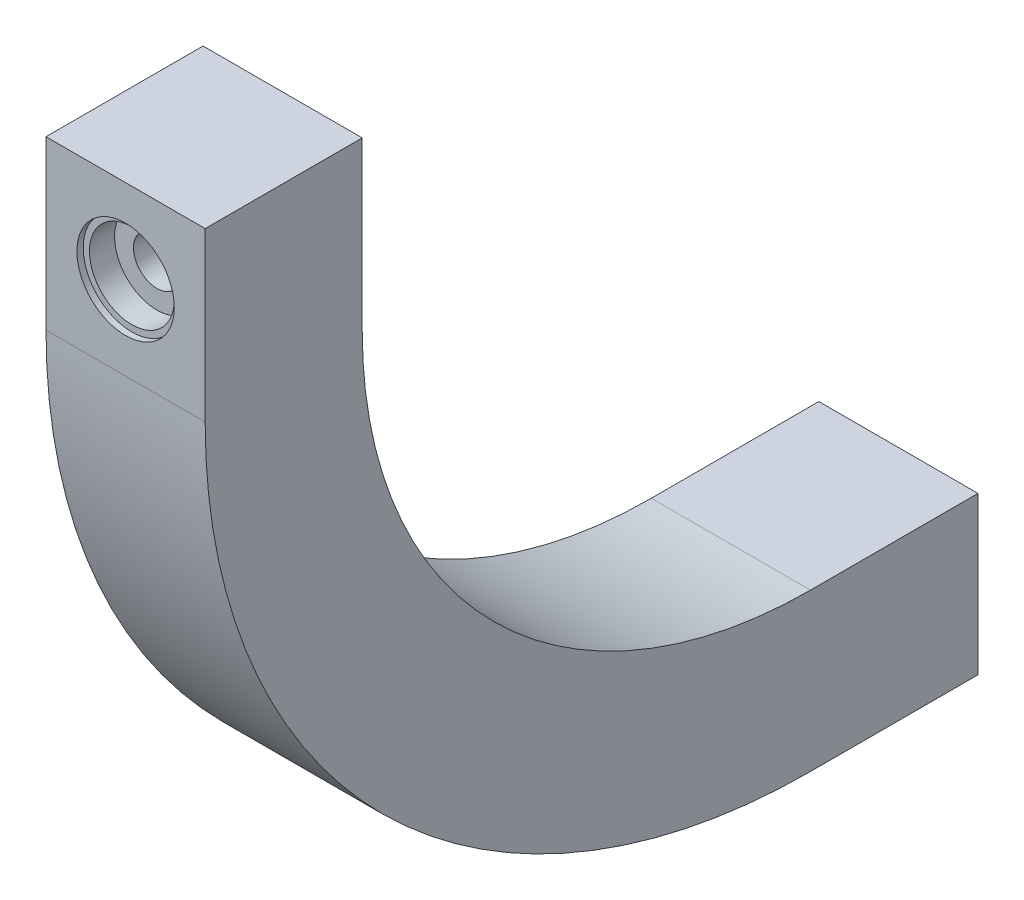
SolidWorks part; units mm, degrees
ref_plane "Front Plane" through (0, 0, 0) normal (0, 0, 1) x (1, 0, 0)
ref_plane "Top Plane" through (0, 0, 0) normal (0, 1, 0) x (1, 0, 0)
ref_plane "Right Plane" through (0, 0, 0) normal (1, 0, 0) x (0, 0, -1)
ref_axis "Z" through (0, 0, 109.5585) along (0, 0, -1)
ref_axis "X" through (8.36, 0, 0) along (-1, 0, 0)
sketch "Sketch4" plane through (0, 0, 0) normal (0, 0, 1) x (1, 0, 0)
  circle A0 centre (0, 0) radius 49.8046 construction
  dimension "D1" = 99.6092
sketch "Sketch5" plane through (0, 0, 0) normal (1, 0, 0) x (0, 0, -1)
  line L0 (-50.8046, 8) -> (-50.8046, 0)
  line L1 (-50.8046, 0) -> (-50.8046, -8)
  line L2 (-65.8046, -8) -> (-65.8046, 8)
  line L6 (-65.8046, 8) -> (-50.8046, 8)
  line L12 (-109.5585, 0) -> (-13.0351, 0) construction
  line L13 (0, 0) -> (-14.9091, -14.9091) construction
  line L14 (0, 0) -> (7.0065, 0) construction
  line L15 (0, -50.8046) -> (-8, -50.8046)
  line L16 (8, -50.8046) -> (0, -50.8046)
  line L17 (-8, -65.8046) -> (8, -65.8046)
  line L18 (8, -65.8046) -> (8, -50.8046)
  circle A0 centre (0, 0) radius 14 construction
  arc A1 (-50.8046, -8) -> (-8, -50.8046) centre (-8, -8) ccw
  arc A2 (-65.8046, -8) -> (-8, -65.8046) centre (-8, -8) ccw
  point P2 (9.4307, -21)
  point P4 (0, -2.1363)
  dimension "D1" = 28
  dimension "D4" = 8
  dimension "D2" = 45
  dimension "D3" = 15
  dimension "D5" = 50.8046
sketch "Sketch6" plane through (0, 0, 0) normal (0, 1, 0) x (1, 0, 0)
  circle A0 centre (0, 0) radius 49.8046 construction
  dimension "D1" = 99.6092
extrude "Boss-Extrude1" add sketch "Sketch5" along normal blind 7.6 and the other way blind 7.6
sketch "Sketch7" plane through (0, 0, 0) normal (0, 0, 1) x (1, 0, 0)
  circle A0 centre (0, 0) radius 2.25
  dimension "D1" = 4.5
extrude "Cut-Extrude1" cut sketch "Sketch7" along normal through all
ref_axis "Y" through (0, -9.3489, 0) along (0, -1, 0)
sketch "Sketch16" plane through (0, 0, 0) normal (1, 0, 0) x (0, 0, -1)
  line L0 (0, -66.8046) -> (0, 0) construction
  dimension "D1" = 66.8046
ref_plane "Plane1" through (0, -66.8046, 0) normal (0, 1, 0) x (1, 0, 0)
ref_axis "CX" through (0, -66.8046, 4.4) along (0, 0, -1)
ref_plane "Plane2" through (0, 0, 0) normal (0, 0, -1) x (0, 1, 0)
ref_plane "Plane3" through (0, 0, 0) normal (1, 0, 0) x (0, 0, -1)
ref_axis "CZ" through (0, -8.7018, 0) along (0, -1, 0)
ref_axis "CY" through (-0.6471, -66.8046, 0) along (1, 0, 0)
ref_point "CO"
sketch "Sketch15" plane through (0, -65.8046, 0) normal (0, -1, 0) x (1, 0, 0)
  circle A0 centre (0, 0) radius 2.05
  dimension "D1" = 4.1
extrude "Cut-Extrude11" cut sketch "Sketch15" against normal blind 10
sketch "Sketch18" plane through (0, 0, 0) normal (1, 0, 0) x (0, 0, -1)
  line L0 (-65.8046, 4.65) -> (-65.8046, 0)
  line L1 (-65.8046, 0) -> (-62.8046, 0)
  line L2 (-62.8046, 0) -> (-62.8046, 4.05)
  line L3 (-62.8046, 4.05) -> (-65.2046, 4.05)
  line L4 (-65.2046, 4.05) -> (-65.2046, 4.65)
  line L5 (-65.2046, 4.65) -> (-65.8046, 4.65)
  line L6 (-68.6876, 0) -> (-58.3046, 0) construction
  line L7 (-58.3046, 0) -> (-58.3046, 8) construction
  line L8 (-51.4046, 4.65) -> (-50.8046, 4.65)
  line L9 (-51.4046, 4.05) -> (-51.4046, 4.65)
  line L10 (-53.8046, 4.05) -> (-51.4046, 4.05)
  line L11 (-53.8046, 0) -> (-53.8046, 4.05)
  line L12 (-50.8046, 0) -> (-53.8046, 0)
  line L13 (-50.8046, 4.65) -> (-50.8046, 0)
  line L14 (-109.5585, 0) -> (-13.0351, 0) construction
  line L15 (-65.8046, 8) -> (-50.8046, 8) construction
  line L16 (-65.8046, -8) -> (-65.8046, 8) construction
  dimension "D1" = 0.6
  dimension "D2" = 8.1
  dimension "D3" = 3
  dimension "D4" = 4.65
revolve "Cut-Revolve1" cut sketch "Sketch18" angle 360 about axis through (0, 0, 109.5585) along (0, 0, -1)
equation "\"rbracket-width\"= \"L2Thickness\" + 0.2"
equation "\"EyeCaptureRadius\"= ( \"EyeDiameter\" + \"EyeClearance\" ) / 2"
equation "\"rbracket_planetocenterline_dist\"= \"BasePlaneDistance\""
equation "\"EyeDiameter\" = 99.60916292"
equation "\"BasePlaneDistance\" = \"EyeDiameter\"/2+\"L2Thickness\"+\"EyeClearance\""
equation "\"EyeClearance\" = 2"
equation "\"D1@Sketch4\"=\"EyeDiameter\""
equation "\"D1@Sketch6\"=\"EyeDiameter\""
equation "\"D1@Boss-Extrude1\"=\"rbracket-width\"/2"
equation "\"D2@Boss-Extrude1\"=\"rbracket-width\"/2"
equation "\"L2Thickness\" = 3.75 * \"shaft_diameter\""
equation "\"D3@Sketch5\"=\"L2Thickness\""
equation "\"D5@Sketch5\"=(\"EyeDiameter\"+\"EyeClearance\")/2"
equation "\"BearingThickness\"= 6"
equation "\"BearingOD\"=4.5"
equation "\"OuterBearingProudDistance\"= 0"
equation "\"FlangeOD\"=7.5"
equation "\"FlangeThickness\"= 0.75"
equation "\"PrinterFilamentThickness\"= 0.1'For setting distances for things like pressfits"
equation "\"ApplyPrinterOffset\"= 1'Set to 0 for line-to-line. Set to 1 for applying guestimate dimensions to make the printer produce good parts"
equation "\"D1@Cut-Extrude11\"=\"shaft_diameter\"*2.5"
equation "\"D1@Sketch16\"=\"BasePlaneDistance\""
equation "\"D2@Sketch18\"=\"ApplyPrinterOffset\"*\"PrinterFilamentThickness\" + 8"
equation "\"D4@Sketch18\"=4.6 + \"ApplyPrinterOffset\"*\"PrinterFilamentThickness\"/2"
equation "\"L2_ID\" = 20"
equation "\"vx\" = 50"
equation "\"vy\" = 10"
equation "\"vz\" = 100"
equation "\"parametric_end\" = 1"
equation "\"Rw_3_xx\" = -(\"vz\")/sqr((\"vx\")^2 + (\"vz\")^2)"
equation "\"Rw_3_xy\" = 0"
equation "\"Rw_3_xz\" = (\"vx\")/sqr((\"vx\")^2 + (\"vz\")^2)"
equation "\"Rw_3_zx\" = (\"vx\")/sqr((\"vx\")^2 + (\"vy\")^2 + (\"vz\")^2)"
equation "\"Rw_3_zy\" = (\"vy\")/sqr((\"vx\")^2 + (\"vy\")^2 + (\"vz\")^2)"
equation "\"Rw_3_zz\" = (\"vz\")/sqr((\"vx\")^2 + (\"vy\")^2 + (\"vz\")^2)"
equation "\"Rw_3_yx\" = (\"vx\")*(\"vy\")/sqr((\"vx\")^4 + (\"vx\")^2*(\"vy\")^2 + 2*(\"vx\")^2*(\"vz\")^2 + (\"vy\")^2*(\"vz\")^2 + (\"vz\")^4)"
equation "\"Rw_3_yy\" = -sqr((\"vx\")^2 + (\"vz\")^2)/sqr((\"vx\")^2 + (\"vy\")^2 + (\"vz\")^2)"
equation "\"Rw_3_yz\" = (\"vy\")*(\"vz\")/sqr((\"vx\")^4 + (\"vx\")^2*(\"vy\")^2 + 2*(\"vx\")^2*(\"vz\")^2 + (\"vy\")^2*(\"vz\")^2 + (\"vz\")^4)"
equation "\"O2Targx\" = -\"BasePlaneDistance\"*(\"vx\")*(\"vy\")/sqr((\"vx\")^4 + (\"vx\")^2*(\"vy\")^2 + 2*(\"vx\")^2*(\"vz\")^2 + (\"vy\")^2*(\"vz\")^2 + (\"vz\")^4)"
equation "\"O2Targy\" = \"BasePlaneDistance\"*sqr((\"vx\")^2 + (\"vz\")^2)/sqr((\"vx\")^2 + (\"vy\")^2 + (\"vz\")^2)"
equation "\"O2Targz\" = -\"BasePlaneDistance\"*(\"vy\")*(\"vz\")/sqr((\"vx\")^4 + (\"vx\")^2*(\"vy\")^2 + 2*(\"vx\")^2*(\"vz\")^2 + (\"vy\")^2*(\"vz\")^2 + (\"vz\")^4)"
equation "\"O2Targx_0\" = -(\"BasePlaneDistance\")*sqr((\"vx\")^2 + (\"vz\")^2)/sqr((\"vx\")^2 + (\"vy\")^2 + (\"vz\")^2)"
equation "\"O2Targy_0\" = -(\"BasePlaneDistance\")*(\"vy\")*(\"vz\")/sqr((\"vx\")^4 + (\"vx\")^2*(\"vy\")^2 + 2*(\"vx\")^2*(\"vz\")^2 + (\"vy\")^2*(\"vz\")^2 + (\"vz\")^4)"
equation "\"O2Targz_0\" = (\"BasePlaneDistance\")*(\"vx\")*(\"vy\")/sqr((\"vx\")^4 + (\"vx\")^2*(\"vy\")^2 + 2*(\"vx\")^2*(\"vz\")^2 + (\"vy\")^2*(\"vz\")^2 + (\"vz\")^4) + (\"BasePlaneDistance\")"
equation "\"theta2_s1\" = arcsin(((\"BasePlaneDistance\") - (\"O2Targz_0\"))/(\"BasePlaneDistance\")) + pi"
equation "\"theta2_s2\" = -arcsin(((\"BasePlaneDistance\") - (\"O2Targz_0\"))/(\"BasePlaneDistance\"))"
equation "\"theta1_s1\" = arcsin((\"O2Targy_0\")/((\"BasePlaneDistance\")*cos((\"Theta2\")))) + pi"
equation "\"theta1_s2\" = -arcsin((\"O2Targy_0\")/((\"BasePlaneDistance\")*cos((\"Theta2\"))))"
equation "\"theta1_s3\" = -arccos(-(\"O2Targx_0\")/((\"BasePlaneDistance\")*cos((\"Theta2\")))) + 2*pi"
equation "\"theta1_s4\" = arccos(-(\"O2Targx_0\")/((\"BasePlaneDistance\")*cos((\"Theta2\"))))"
equation "\"Theta1\" = \"theta1_s2\" 'so far, theta1_s1 and theta1_s4 have agreed, and they agree with the sw constraint solver"
equation "\"Theta2\" = \"theta2_s2\""
equation "\"o2_x\" = -(\"BasePlaneDistance\")*cos((\"Theta1\"))*cos((\"Theta2\"))"
equation "\"o2_y\" = -(\"BasePlaneDistance\")*sin((\"Theta1\"))*cos((\"Theta2\"))"
equation "\"o2_z\" = (\"BasePlaneDistance\")*(sin((\"Theta2\")) + 1)"
equation "\"o1_x\" = (\"BasePlaneDistance\")*sin((\"Theta1\"))"
equation "\"o1_y\" = -(\"BasePlaneDistance\")*cos((\"Theta1\"))"
equation "\"o1_z\" = (\"BasePlaneDistance\")"
equation "\"Actuator1_Theta\" = atn(\"vx\"/\"vz\") 'ik solution for the single link joint"
equation "\"Actuator2_Theta\" = \"Theta1\"  'ik solution for the double link joint"
equation "\"MotorBaseThickness\" = 3 "
equation "\"BaseThickness\" = 3 "
equation "\"EncoderToMagnetAirgap\" = 1 'Encoder to magnet airgap"
equation "\"EncoderHeight\" = 1.192  'Height of the encoder"
equation "\"MagnetThickness\" = 0.5  'Magnet thickness"
equation "\"pcb_thickness\" = 1.6  'Thickness of the PCB"
equation "\"pcb_outer_diameter\" = 32 'the OD of the pcb"
equation "\"shaft_diameter\" = 4"
equation "\"D1@Sketch15\"=\"shaft_diameter\"+\"ApplyPrinterOffset\"*\"PrinterFilamentThickness\""
